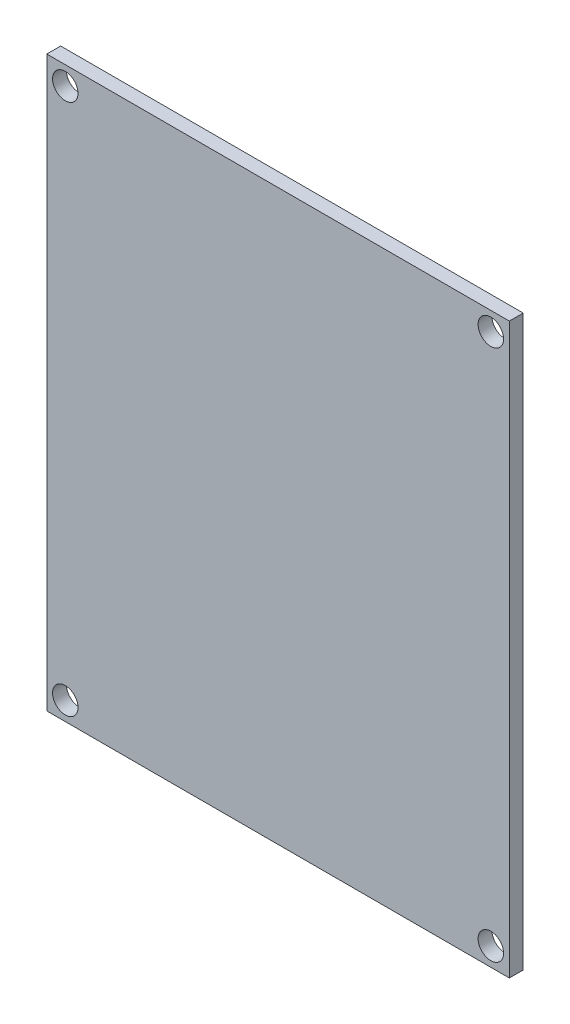
SolidWorks part; units mm, degrees
ref_plane "Front Plane" through (0, 0, 0) normal (0, 0, 1) x (1, 0, 0)
ref_plane "Top Plane" through (0, 0, 0) normal (0, 1, 0) x (1, 0, 0)
ref_plane "Right Plane" through (0, 0, 0) normal (1, 0, 0) x (0, 0, -1)
sketch "Model" plane through (0, 0, 0) normal (0, 0, 1) x (1, 0, 0)
  line L0 (84.1673, 32.1811) -> (4.1672, 32.1811)
  line L1 (84.1673, 130.5807) -> (84.1673, 32.1811)
  line L2 (4.1672, 130.5807) -> (84.1673, 130.5807)
  line L3 (4.1672, 32.1811) -> (4.1672, 130.5807)
  line L4 (36.7661, 123.577) -> (38.7714, 123.577)
  line L5 (38.7714, 123.577) -> (38.7714, 125.5823)
  line L6 (38.7714, 125.5823) -> (36.7661, 125.5823)
  line L7 (36.7661, 125.5823) -> (36.7661, 123.577)
  line L8 (62.7636, 124.3784) -> (64.7689, 124.3784)
  line L9 (64.7689, 124.3784) -> (64.7689, 126.3837)
  line L10 (64.7689, 126.3837) -> (62.7636, 126.3837)
  line L11 (62.7636, 126.3837) -> (62.7636, 124.3784)
  line L12 (5.8947, 120.0139) -> (7.5208, 120.0139)
  line L13 (7.5208, 120.0139) -> (7.5208, 121.64)
  line L14 (7.5208, 121.64) -> (5.8947, 121.64)
  line L15 (5.8947, 121.64) -> (5.8947, 120.0139)
  line L16 (5.8947, 103.7586) -> (7.5208, 103.7586)
  line L17 (7.5208, 103.7586) -> (7.5208, 105.3846)
  line L18 (7.5208, 105.3846) -> (5.8947, 105.3846)
  line L19 (5.8947, 105.3846) -> (5.8947, 103.7586)
  line L20 (5.8947, 87.5021) -> (7.5208, 87.5021)
  line L21 (7.5208, 87.5021) -> (7.5208, 89.1282)
  line L22 (7.5208, 89.1282) -> (5.8947, 89.1282)
  line L23 (5.8947, 89.1282) -> (5.8947, 87.5021)
  line L24 (5.8947, 71.2457) -> (7.5208, 71.2457)
  line L25 (7.5208, 71.2457) -> (7.5208, 72.8718)
  line L26 (7.5208, 72.8718) -> (5.8947, 72.8718)
  line L27 (5.8947, 72.8718) -> (5.8947, 71.2457)
  line L28 (5.8947, 54.9903) -> (7.5208, 54.9903)
  line L29 (7.5208, 54.9903) -> (7.5208, 56.6164)
  line L30 (7.5208, 56.6164) -> (5.8947, 56.6164)
  line L31 (5.8947, 56.6164) -> (5.8947, 54.9903)
  line L32 (69.5711, 125.1678) -> (71.1972, 125.1678)
  line L33 (71.1972, 125.1678) -> (71.1972, 126.7938)
  line L34 (71.1972, 126.7938) -> (69.5711, 126.7938)
  line L35 (69.5711, 126.7938) -> (69.5711, 125.1678)
  line L36 (5.8947, 46.8621) -> (7.5208, 46.8621)
  line L37 (7.5208, 46.8621) -> (7.5208, 48.4882)
  line L38 (7.5208, 48.4882) -> (5.8947, 48.4882)
  line L39 (5.8947, 48.4882) -> (5.8947, 46.8621)
  line L40 (5.8947, 40.7657) -> (7.5208, 40.7657)
  line L41 (7.5208, 40.7657) -> (7.5208, 42.3918)
  line L42 (7.5208, 42.3918) -> (5.8947, 42.3918)
  line L43 (5.8947, 42.3918) -> (5.8947, 40.7657)
  line L44 (43.1315, 46.4697) -> (44.3387, 46.4697)
  line L45 (44.3387, 46.4697) -> (44.3387, 47.6768)
  line L46 (44.3387, 47.6768) -> (43.1315, 47.6768)
  line L47 (43.1315, 47.6768) -> (43.1315, 46.4697)
  line L48 (47.571, 110.5672) -> (49.1971, 110.5672)
  line L49 (49.1971, 110.5672) -> (49.1971, 112.1933)
  line L50 (49.1971, 112.1933) -> (47.571, 112.1933)
  line L51 (47.571, 112.1933) -> (47.571, 110.5672)
  line L52 (79.138, 119.3513) -> (80.7641, 119.3513)
  line L53 (80.7641, 119.3513) -> (80.7641, 120.9774)
  line L54 (80.7641, 120.9774) -> (79.138, 120.9774)
  line L55 (79.138, 120.9774) -> (79.138, 119.3513)
  line L56 (39.5839, 36.2799) -> (39.5839, 36.0803)
  line L57 (40.7899, 36.0803) -> (40.7899, 36.2799)
  line L58 (43.1436, 36.2799) -> (43.1436, 36.0803)
  line L59 (44.3508, 36.0803) -> (44.3508, 36.2799)
  line L60 (44.2835, 33.7156) -> (44.2835, 33.5558)
  line L61 (46.2095, 33.5558) -> (46.2095, 33.7156)
  line L62 (37.7241, 33.7156) -> (37.7241, 33.5558)
  line L63 (39.65, 33.5558) -> (39.65, 33.7156)
  line L64 (67.202, 45.6494) -> (68.828, 45.6494)
  line L65 (68.828, 45.6494) -> (68.828, 47.2755)
  line L66 (68.828, 47.2755) -> (67.202, 47.2755)
  line L67 (67.202, 47.2755) -> (67.202, 45.6494)
  line L68 (24.7396, 63.1693) -> (26.3657, 63.1693)
  line L69 (26.3657, 63.1693) -> (26.3657, 64.7954)
  line L70 (26.3657, 64.7954) -> (24.7396, 64.7954)
  line L71 (24.7396, 64.7954) -> (24.7396, 63.1693)
  line L72 (24.7396, 60.9688) -> (26.3657, 60.9688)
  line L73 (26.3657, 60.9688) -> (26.3657, 62.5949)
  line L74 (26.3657, 62.5949) -> (24.7396, 62.5949)
  line L75 (24.7396, 62.5949) -> (24.7396, 60.9688)
  line L76 (24.7396, 93.3682) -> (26.3657, 93.3682)
  line L77 (26.3657, 93.3682) -> (26.3657, 94.9942)
  line L78 (26.3657, 94.9942) -> (24.7396, 94.9942)
  line L79 (24.7396, 94.9942) -> (24.7396, 93.3682)
  line L80 (24.7396, 95.5675) -> (26.3657, 95.5675)
  line L81 (26.3657, 95.5675) -> (26.3657, 97.1936)
  line L82 (26.3657, 97.1936) -> (24.7396, 97.1936)
  line L83 (24.7396, 97.1936) -> (24.7396, 95.5675)
  line L84 (24.7396, 79.3684) -> (26.3657, 79.3684)
  line L85 (26.3657, 79.3684) -> (26.3657, 80.9945)
  line L86 (26.3657, 80.9945) -> (24.7396, 80.9945)
  line L87 (24.7396, 80.9945) -> (24.7396, 79.3684)
  line L88 (24.7396, 77.1679) -> (26.3657, 77.1679)
  line L89 (26.3657, 77.1679) -> (26.3657, 78.794)
  line L90 (26.3657, 78.794) -> (24.7396, 78.794)
  line L91 (24.7396, 78.794) -> (24.7396, 77.1679)
  line L92 (24.7396, 109.3688) -> (26.3657, 109.3688)
  line L93 (26.3657, 109.3688) -> (26.3657, 110.9949)
  line L94 (26.3657, 110.9949) -> (24.7396, 110.9949)
  line L95 (24.7396, 110.9949) -> (24.7396, 109.3688)
  line L96 (24.7396, 111.5693) -> (26.3657, 111.5693)
  line L97 (26.3657, 111.5693) -> (26.3657, 113.1954)
  line L98 (26.3657, 113.1954) -> (24.7396, 113.1954)
  line L99 (24.7396, 113.1954) -> (24.7396, 111.5693)
  line L100 (39.3623, 114.5525) -> (40.9884, 114.5525)
  line L101 (40.9884, 114.5525) -> (40.9884, 116.1785)
  line L102 (40.9884, 116.1785) -> (39.3623, 116.1785)
  line L103 (39.3623, 116.1785) -> (39.3623, 114.5525)
  line L104 (9.9594, 103.7586) -> (11.5854, 103.7586)
  line L105 (11.5854, 103.7586) -> (11.5854, 105.3846)
  line L106 (11.5854, 105.3846) -> (9.9594, 105.3846)
  line L107 (9.9594, 105.3846) -> (9.9594, 103.7586)
  line L108 (84.1673, 32.1811) -> (4.1672, 32.1811)
  line L109 (84.1673, 130.5807) -> (84.1673, 32.1811)
  line L110 (4.1672, 130.5807) -> (84.1673, 130.5807)
  line L111 (4.1672, 32.1811) -> (4.1672, 130.5807)
  spline S0 degree 3 poles (44.9703, 124.5802) (44.9703, 126.1842) (42.5648, 126.1842) (42.5648, 124.5802) knots 0 0 0 0 1 1 1 1
  spline S1 degree 3 poles (42.5648, 124.5802) (42.5648, 122.9761) (44.9703, 122.9761) (44.9703, 124.5802) knots 0 0 0 0 1 1 1 1
  spline S2 degree 3 poles (60.9699, 125.3805) (60.9699, 126.9846) (58.5644, 126.9846) (58.5644, 125.3805) knots 0 0 0 0 1 1 1 1
  spline S3 degree 3 poles (58.5644, 125.3805) (58.5644, 123.7765) (60.9699, 123.7765) (60.9699, 125.3805) knots 0 0 0 0 1 1 1 1
  spline S4 degree 3 poles (7.5208, 118.7946) (7.5208, 119.8783) (5.8947, 119.8783) (5.8947, 118.7946) knots 0 0 0 0 1 1 1 1
  spline S5 degree 3 poles (5.8947, 118.7946) (5.8947, 117.7109) (7.5208, 117.7109) (7.5208, 118.7946) knots 0 0 0 0 1 1 1 1
  spline S6 degree 3 poles (7.5208, 116.7628) (7.5208, 117.8465) (5.8947, 117.8465) (5.8947, 116.7628) knots 0 0 0 0 1 1 1 1
  spline S7 degree 3 poles (5.8947, 116.7628) (5.8947, 115.6791) (7.5208, 115.6791) (7.5208, 116.7628) knots 0 0 0 0 1 1 1 1
  spline S8 degree 3 poles (7.5208, 114.731) (7.5208, 115.8147) (5.8947, 115.8147) (5.8947, 114.731) knots 0 0 0 0 1 1 1 1
  spline S9 degree 3 poles (5.8947, 114.731) (5.8947, 113.6474) (7.5208, 113.6474) (7.5208, 114.731) knots 0 0 0 0 1 1 1 1
  spline S10 degree 3 poles (7.5208, 112.6993) (7.5208, 113.783) (5.8947, 113.783) (5.8947, 112.6993) knots 0 0 0 0 1 1 1 1
  spline S11 degree 3 poles (5.8947, 112.6993) (5.8947, 111.6156) (7.5208, 111.6156) (7.5208, 112.6993) knots 0 0 0 0 1 1 1 1
  spline S12 degree 3 poles (7.5208, 110.6675) (7.5208, 111.7512) (5.8947, 111.7512) (5.8947, 110.6675) knots 0 0 0 0 1 1 1 1
  spline S13 degree 3 poles (5.8947, 110.6675) (5.8947, 109.5827) (7.5208, 109.5827) (7.5208, 110.6675) knots 0 0 0 0 1 1 1 1
  spline S14 degree 3 poles (7.5208, 108.6346) (7.5208, 109.7183) (5.8947, 109.7183) (5.8947, 108.6346) knots 0 0 0 0 1 1 1 1
  spline S15 degree 3 poles (5.8947, 108.6346) (5.8947, 107.5509) (7.5208, 107.5509) (7.5208, 108.6346) knots 0 0 0 0 1 1 1 1
  spline S16 degree 3 poles (7.5208, 102.5393) (7.5208, 103.623) (5.8947, 103.623) (5.8947, 102.5393) knots 0 0 0 0 1 1 1 1
  spline S17 degree 3 poles (5.8947, 102.5393) (5.8947, 101.4556) (7.5208, 101.4556) (7.5208, 102.5393) knots 0 0 0 0 1 1 1 1
  spline S18 degree 3 poles (7.5208, 100.5075) (7.5208, 101.5912) (5.8947, 101.5912) (5.8947, 100.5075) knots 0 0 0 0 1 1 1 1
  spline S19 degree 3 poles (5.8947, 100.5075) (5.8947, 99.4227) (7.5208, 99.4227) (7.5208, 100.5075) knots 0 0 0 0 1 1 1 1
  spline S20 degree 3 poles (7.5208, 98.4746) (7.5208, 99.5583) (5.8947, 99.5583) (5.8947, 98.4746) knots 0 0 0 0 1 1 1 1
  spline S21 degree 3 poles (5.8947, 98.4746) (5.8947, 97.3909) (7.5208, 97.3909) (7.5208, 98.4746) knots 0 0 0 0 1 1 1 1
  spline S22 degree 3 poles (7.5208, 96.4428) (7.5208, 97.5265) (5.8947, 97.5265) (5.8947, 96.4428) knots 0 0 0 0 1 1 1 1
  spline S23 degree 3 poles (5.8947, 96.4428) (5.8947, 95.3591) (7.5208, 95.3591) (7.5208, 96.4428) knots 0 0 0 0 1 1 1 1
  spline S24 degree 3 poles (7.5208, 94.4111) (7.5208, 95.4947) (5.8947, 95.4947) (5.8947, 94.4111) knots 0 0 0 0 1 1 1 1
  spline S25 degree 3 poles (5.8947, 94.4111) (5.8947, 93.3274) (7.5208, 93.3274) (7.5208, 94.4111) knots 0 0 0 0 1 1 1 1
  spline S26 degree 3 poles (7.5208, 92.3793) (7.5208, 93.463) (5.8947, 93.463) (5.8947, 92.3793) knots 0 0 0 0 1 1 1 1
  spline S27 degree 3 poles (5.8947, 92.3793) (5.8947, 91.2956) (7.5208, 91.2956) (7.5208, 92.3793) knots 0 0 0 0 1 1 1 1
  spline S28 degree 3 poles (7.5208, 86.2828) (7.5208, 87.3665) (5.8947, 87.3665) (5.8947, 86.2828) knots 0 0 0 0 1 1 1 1
  spline S29 degree 3 poles (5.8947, 86.2828) (5.8947, 85.1991) (7.5208, 85.1991) (7.5208, 86.2828) knots 0 0 0 0 1 1 1 1
  spline S30 degree 3 poles (7.5208, 84.2511) (7.5208, 85.3347) (5.8947, 85.3347) (5.8947, 84.2511) knots 0 0 0 0 1 1 1 1
  spline S31 degree 3 poles (5.8947, 84.2511) (5.8947, 83.1674) (7.5208, 83.1674) (7.5208, 84.2511) knots 0 0 0 0 1 1 1 1
  spline S32 degree 3 poles (7.5208, 82.2193) (7.5208, 83.303) (5.8947, 83.303) (5.8947, 82.2193) knots 0 0 0 0 1 1 1 1
  spline S33 degree 3 poles (5.8947, 82.2193) (5.8947, 81.1356) (7.5208, 81.1356) (7.5208, 82.2193) knots 0 0 0 0 1 1 1 1
  spline S34 degree 3 poles (7.5208, 80.1875) (7.5208, 81.2712) (5.8947, 81.2712) (5.8947, 80.1875) knots 0 0 0 0 1 1 1 1
  spline S35 degree 3 poles (5.8947, 80.1875) (5.8947, 79.1027) (7.5208, 79.1027) (7.5208, 80.1875) knots 0 0 0 0 1 1 1 1
  spline S36 degree 3 poles (7.5208, 78.1546) (7.5208, 79.2383) (5.8947, 79.2383) (5.8947, 78.1546) knots 0 0 0 0 1 1 1 1
  spline S37 degree 3 poles (5.8947, 78.1546) (5.8947, 77.0709) (7.5208, 77.0709) (7.5208, 78.1546) knots 0 0 0 0 1 1 1 1
  spline S38 degree 3 poles (7.5208, 76.1228) (7.5208, 77.2065) (5.8947, 77.2065) (5.8947, 76.1228) knots 0 0 0 0 1 1 1 1
  spline S39 degree 3 poles (5.8947, 76.1228) (5.8947, 75.0391) (7.5208, 75.0391) (7.5208, 76.1228) knots 0 0 0 0 1 1 1 1
  spline S40 degree 3 poles (7.5208, 70.0275) (7.5208, 71.1112) (5.8947, 71.1112) (5.8947, 70.0275) knots 0 0 0 0 1 1 1 1
  spline S41 degree 3 poles (5.8947, 70.0275) (5.8947, 68.9427) (7.5208, 68.9427) (7.5208, 70.0275) knots 0 0 0 0 1 1 1 1
  spline S42 degree 3 poles (7.5208, 67.9946) (7.5208, 69.0783) (5.8947, 69.0783) (5.8947, 67.9946) knots 0 0 0 0 1 1 1 1
  spline S43 degree 3 poles (5.8947, 67.9946) (5.8947, 66.9109) (7.5208, 66.9109) (7.5208, 67.9946) knots 0 0 0 0 1 1 1 1
  spline S44 degree 3 poles (7.5208, 65.9628) (7.5208, 67.0465) (5.8947, 67.0465) (5.8947, 65.9628) knots 0 0 0 0 1 1 1 1
  spline S45 degree 3 poles (5.8947, 65.9628) (5.8947, 64.8791) (7.5208, 64.8791) (7.5208, 65.9628) knots 0 0 0 0 1 1 1 1
  spline S46 degree 3 poles (7.5208, 63.9311) (7.5208, 65.0147) (5.8947, 65.0147) (5.8947, 63.9311) knots 0 0 0 0 1 1 1 1
  spline S47 degree 3 poles (5.8947, 63.9311) (5.8947, 62.8474) (7.5208, 62.8474) (7.5208, 63.9311) knots 0 0 0 0 1 1 1 1
  spline S48 degree 3 poles (7.5208, 61.8993) (7.5208, 62.983) (5.8947, 62.983) (5.8947, 61.8993) knots 0 0 0 0 1 1 1 1
  spline S49 degree 3 poles (5.8947, 61.8993) (5.8947, 60.8156) (7.5208, 60.8156) (7.5208, 61.8993) knots 0 0 0 0 1 1 1 1
  spline S50 degree 3 poles (7.5208, 59.8675) (7.5208, 60.9512) (5.8947, 60.9512) (5.8947, 59.8675) knots 0 0 0 0 1 1 1 1
  spline S51 degree 3 poles (5.8947, 59.8675) (5.8947, 58.7827) (7.5208, 58.7827) (7.5208, 59.8675) knots 0 0 0 0 1 1 1 1
  spline S52 degree 3 poles (7.5208, 53.7711) (7.5208, 54.8547) (5.8947, 54.8547) (5.8947, 53.7711) knots 0 0 0 0 1 1 1 1
  spline S53 degree 3 poles (5.8947, 53.7711) (5.8947, 52.6874) (7.5208, 52.6874) (7.5208, 53.7711) knots 0 0 0 0 1 1 1 1
  spline S54 degree 3 poles (7.5208, 51.7393) (7.5208, 52.823) (5.8947, 52.823) (5.8947, 51.7393) knots 0 0 0 0 1 1 1 1
  spline S55 degree 3 poles (5.8947, 51.7393) (5.8947, 50.6556) (7.5208, 50.6556) (7.5208, 51.7393) knots 0 0 0 0 1 1 1 1
  spline S56 degree 3 poles (7.5208, 49.7075) (7.5208, 50.7912) (5.8947, 50.7912) (5.8947, 49.7075) knots 0 0 0 0 1 1 1 1
  spline S57 degree 3 poles (5.8947, 49.7075) (5.8947, 48.6227) (7.5208, 48.6227) (7.5208, 49.7075) knots 0 0 0 0 1 1 1 1
  spline S58 degree 3 poles (69.1654, 125.9803) (69.1654, 127.0639) (67.5393, 127.0639) (67.5393, 125.9803) knots 0 0 0 0 1 1 1 1
  spline S59 degree 3 poles (67.5393, 125.9803) (67.5393, 124.8966) (69.1654, 124.8966) (69.1654, 125.9803) knots 0 0 0 0 1 1 1 1
  spline S60 degree 3 poles (7.5208, 45.6428) (7.5208, 46.7265) (5.8947, 46.7265) (5.8947, 45.6428) knots 0 0 0 0 1 1 1 1
  spline S61 degree 3 poles (5.8947, 45.6428) (5.8947, 44.5591) (7.5208, 44.5591) (7.5208, 45.6428) knots 0 0 0 0 1 1 1 1
  spline S62 degree 3 poles (7.5208, 39.5475) (7.5208, 40.6312) (5.8947, 40.6312) (5.8947, 39.5475) knots 0 0 0 0 1 1 1 1
  spline S63 degree 3 poles (5.8947, 39.5475) (5.8947, 38.4627) (7.5208, 38.4627) (7.5208, 39.5475) knots 0 0 0 0 1 1 1 1
  spline S64 degree 3 poles (44.3387, 48.0891) (44.3387, 48.8939) (43.1315, 48.8939) (43.1315, 48.0891) knots 0 0 0 0 1 1 1 1
  spline S65 degree 3 poles (43.1315, 48.0891) (43.1315, 47.2843) (44.3387, 47.2843) (44.3387, 48.0891) knots 0 0 0 0 1 1 1 1
  spline S66 degree 3 poles (45.354, 47.0738) (45.354, 47.8786) (44.1468, 47.8786) (44.1468, 47.0738) knots 0 0 0 0 1 1 1 1
  spline S67 degree 3 poles (44.1468, 47.0738) (44.1468, 46.269) (45.354, 46.269) (45.354, 47.0738) knots 0 0 0 0 1 1 1 1
  spline S68 degree 3 poles (45.354, 48.0891) (45.354, 48.8939) (44.1468, 48.8939) (44.1468, 48.0891) knots 0 0 0 0 1 1 1 1
  spline S69 degree 3 poles (44.1468, 48.0891) (44.1468, 47.2843) (45.354, 47.2843) (45.354, 48.0891) knots 0 0 0 0 1 1 1 1
  spline S70 degree 3 poles (46.3704, 47.0738) (46.3704, 47.8786) (45.1633, 47.8786) (45.1633, 47.0738) knots 0 0 0 0 1 1 1 1
  spline S71 degree 3 poles (45.1633, 47.0738) (45.1633, 46.269) (46.3704, 46.269) (46.3704, 47.0738) knots 0 0 0 0 1 1 1 1
  spline S72 degree 3 poles (46.3704, 48.0891) (46.3704, 48.8939) (45.1633, 48.8939) (45.1633, 48.0891) knots 0 0 0 0 1 1 1 1
  spline S73 degree 3 poles (45.1633, 48.0891) (45.1633, 47.2843) (46.3704, 47.2843) (46.3704, 48.0891) knots 0 0 0 0 1 1 1 1
  spline S74 degree 3 poles (47.3858, 47.0738) (47.3858, 47.8786) (46.1797, 47.8786) (46.1797, 47.0738) knots 0 0 0 0 1 1 1 1
  spline S75 degree 3 poles (46.1797, 47.0738) (46.1797, 46.269) (47.3858, 46.269) (47.3858, 47.0738) knots 0 0 0 0 1 1 1 1
  spline S76 degree 3 poles (47.3858, 48.0891) (47.3858, 48.8939) (46.1797, 48.8939) (46.1797, 48.0891) knots 0 0 0 0 1 1 1 1
  spline S77 degree 3 poles (46.1797, 48.0891) (46.1797, 47.2843) (47.3858, 47.2843) (47.3858, 48.0891) knots 0 0 0 0 1 1 1 1
  spline S78 degree 3 poles (48.4022, 47.0738) (48.4022, 47.8786) (47.1951, 47.8786) (47.1951, 47.0738) knots 0 0 0 0 1 1 1 1
  spline S79 degree 3 poles (47.1951, 47.0738) (47.1951, 46.269) (48.4022, 46.269) (48.4022, 47.0738) knots 0 0 0 0 1 1 1 1
  spline S80 degree 3 poles (48.4022, 48.0891) (48.4022, 48.8939) (47.1951, 48.8939) (47.1951, 48.0891) knots 0 0 0 0 1 1 1 1
  spline S81 degree 3 poles (47.1951, 48.0891) (47.1951, 47.2843) (48.4022, 47.2843) (48.4022, 48.0891) knots 0 0 0 0 1 1 1 1
  spline S82 degree 3 poles (47.1653, 111.3797) (47.1653, 112.4645) (45.5392, 112.4645) (45.5392, 111.3797) knots 0 0 0 0 1 1 1 1
  spline S83 degree 3 poles (45.5392, 111.3797) (45.5392, 110.296) (47.1653, 110.296) (47.1653, 111.3797) knots 0 0 0 0 1 1 1 1
  spline S84 degree 3 poles (51.4284, 35.9811) (51.4284, 36.7859) (50.2212, 36.7859) (50.2212, 35.9811) knots 0 0 0 0 1 1 1 1
  spline S85 degree 3 poles (50.2212, 35.9811) (50.2212, 35.1764) (51.4284, 35.1764) (51.4284, 35.9811) knots 0 0 0 0 1 1 1 1
  spline S86 degree 3 poles (57.8126, 35.9811) (57.8126, 36.7859) (56.6054, 36.7859) (56.6054, 35.9811) knots 0 0 0 0 1 1 1 1
  spline S87 degree 3 poles (56.6054, 35.9811) (56.6054, 35.1764) (57.8126, 35.1764) (57.8126, 35.9811) knots 0 0 0 0 1 1 1 1
  spline S88 degree 3 poles (82.7958, 120.1649) (82.7958, 121.2486) (81.1698, 121.2486) (81.1698, 120.1649) knots 0 0 0 0 1 1 1 1
  spline S89 degree 3 poles (81.1698, 120.1649) (81.1698, 119.0812) (82.7958, 119.0812) (82.7958, 120.1649) knots 0 0 0 0 1 1 1 1
  spline S90 degree 3 poles (80.7641, 110.0049) (80.7641, 111.0886) (79.138, 111.0886) (79.138, 110.0049) knots 0 0 0 0 1 1 1 1
  spline S91 degree 3 poles (79.138, 110.0049) (79.138, 108.9212) (80.7641, 108.9212) (80.7641, 110.0049) knots 0 0 0 0 1 1 1 1
  spline S92 degree 3 poles (82.7958, 118.132) (82.7958, 119.2157) (81.1698, 119.2157) (81.1698, 118.132) knots 0 0 0 0 1 1 1 1
  spline S93 degree 3 poles (81.1698, 118.132) (81.1698, 117.0484) (82.7958, 117.0484) (82.7958, 118.132) knots 0 0 0 0 1 1 1 1
  spline S94 degree 3 poles (80.7641, 107.972) (80.7641, 109.0557) (79.138, 109.0557) (79.138, 107.972) knots 0 0 0 0 1 1 1 1
  spline S95 degree 3 poles (79.138, 107.972) (79.138, 106.8884) (80.7641, 106.8884) (80.7641, 107.972) knots 0 0 0 0 1 1 1 1
  spline S96 degree 3 poles (82.7958, 116.1003) (82.7958, 117.184) (81.1698, 117.184) (81.1698, 116.1003) knots 0 0 0 0 1 1 1 1
  spline S97 degree 3 poles (81.1698, 116.1003) (81.1698, 115.0166) (82.7958, 115.0166) (82.7958, 116.1003) knots 0 0 0 0 1 1 1 1
  spline S98 degree 3 poles (80.7641, 105.9403) (80.7641, 107.024) (79.138, 107.024) (79.138, 105.9403) knots 0 0 0 0 1 1 1 1
  spline S99 degree 3 poles (79.138, 105.9403) (79.138, 104.8566) (80.7641, 104.8566) (80.7641, 105.9403) knots 0 0 0 0 1 1 1 1
  spline S100 degree 3 poles (82.7958, 114.0685) (82.7958, 115.1522) (81.1698, 115.1522) (81.1698, 114.0685) knots 0 0 0 0 1 1 1 1
  spline S101 degree 3 poles (81.1698, 114.0685) (81.1698, 112.9848) (82.7958, 112.9848) (82.7958, 114.0685) knots 0 0 0 0 1 1 1 1
  spline S102 degree 3 poles (80.7641, 103.9085) (80.7641, 104.9922) (79.138, 104.9922) (79.138, 103.9085) knots 0 0 0 0 1 1 1 1
  spline S103 degree 3 poles (79.138, 103.9085) (79.138, 102.8248) (80.7641, 102.8248) (80.7641, 103.9085) knots 0 0 0 0 1 1 1 1
  spline S104 degree 3 poles (82.7958, 112.0367) (82.7958, 113.1204) (81.1698, 113.1204) (81.1698, 112.0367) knots 0 0 0 0 1 1 1 1
  spline S105 degree 3 poles (81.1698, 112.0367) (81.1698, 110.953) (82.7958, 110.953) (82.7958, 112.0367) knots 0 0 0 0 1 1 1 1
  spline S106 degree 3 poles (80.7641, 101.8767) (80.7641, 102.9604) (79.138, 102.9604) (79.138, 101.8767) knots 0 0 0 0 1 1 1 1
  spline S107 degree 3 poles (79.138, 101.8767) (79.138, 100.793) (80.7641, 100.793) (80.7641, 101.8767) knots 0 0 0 0 1 1 1 1
  spline S108 degree 3 poles (82.7958, 110.0049) (82.7958, 111.0886) (81.1698, 111.0886) (81.1698, 110.0049) knots 0 0 0 0 1 1 1 1
  spline S109 degree 3 poles (81.1698, 110.0049) (81.1698, 108.9212) (82.7958, 108.9212) (82.7958, 110.0049) knots 0 0 0 0 1 1 1 1
  spline S110 degree 3 poles (80.7641, 99.8449) (80.7641, 100.9286) (79.138, 100.9286) (79.138, 99.8449) knots 0 0 0 0 1 1 1 1
  spline S111 degree 3 poles (79.138, 99.8449) (79.138, 98.7612) (80.7641, 98.7612) (80.7641, 99.8449) knots 0 0 0 0 1 1 1 1
  spline S112 degree 3 poles (82.7958, 107.972) (82.7958, 109.0557) (81.1698, 109.0557) (81.1698, 107.972) knots 0 0 0 0 1 1 1 1
  spline S113 degree 3 poles (81.1698, 107.972) (81.1698, 106.8884) (82.7958, 106.8884) (82.7958, 107.972) knots 0 0 0 0 1 1 1 1
  spline S114 degree 3 poles (80.7641, 97.812) (80.7641, 98.8957) (79.138, 98.8957) (79.138, 97.812) knots 0 0 0 0 1 1 1 1
  spline S115 degree 3 poles (79.138, 97.812) (79.138, 96.7284) (80.7641, 96.7284) (80.7641, 97.812) knots 0 0 0 0 1 1 1 1
  spline S116 degree 3 poles (82.7958, 105.9403) (82.7958, 107.024) (81.1698, 107.024) (81.1698, 105.9403) knots 0 0 0 0 1 1 1 1
  spline S117 degree 3 poles (81.1698, 105.9403) (81.1698, 104.8566) (82.7958, 104.8566) (82.7958, 105.9403) knots 0 0 0 0 1 1 1 1
  spline S118 degree 3 poles (80.7641, 95.7803) (80.7641, 96.864) (79.138, 96.864) (79.138, 95.7803) knots 0 0 0 0 1 1 1 1
  spline S119 degree 3 poles (79.138, 95.7803) (79.138, 94.6966) (80.7641, 94.6966) (80.7641, 95.7803) knots 0 0 0 0 1 1 1 1
  spline S120 degree 3 poles (82.7958, 103.9085) (82.7958, 104.9922) (81.1698, 104.9922) (81.1698, 103.9085) knots 0 0 0 0 1 1 1 1
  spline S121 degree 3 poles (81.1698, 103.9085) (81.1698, 102.8248) (82.7958, 102.8248) (82.7958, 103.9085) knots 0 0 0 0 1 1 1 1
  spline S122 degree 3 poles (80.7641, 93.7485) (80.7641, 94.8322) (79.138, 94.8322) (79.138, 93.7485) knots 0 0 0 0 1 1 1 1
  spline S123 degree 3 poles (79.138, 93.7485) (79.138, 92.6648) (80.7641, 92.6648) (80.7641, 93.7485) knots 0 0 0 0 1 1 1 1
  spline S124 degree 3 poles (82.7958, 101.8767) (82.7958, 102.9604) (81.1698, 102.9604) (81.1698, 101.8767) knots 0 0 0 0 1 1 1 1
  spline S125 degree 3 poles (81.1698, 101.8767) (81.1698, 100.793) (82.7958, 100.793) (82.7958, 101.8767) knots 0 0 0 0 1 1 1 1
  spline S126 degree 3 poles (80.7641, 91.7167) (80.7641, 92.8004) (79.138, 92.8004) (79.138, 91.7167) knots 0 0 0 0 1 1 1 1
  spline S127 degree 3 poles (79.138, 91.7167) (79.138, 90.633) (80.7641, 90.633) (80.7641, 91.7167) knots 0 0 0 0 1 1 1 1
  spline S128 degree 3 poles (82.7958, 99.8449) (82.7958, 100.9286) (81.1698, 100.9286) (81.1698, 99.8449) knots 0 0 0 0 1 1 1 1
  spline S129 degree 3 poles (81.1698, 99.8449) (81.1698, 98.7612) (82.7958, 98.7612) (82.7958, 99.8449) knots 0 0 0 0 1 1 1 1
  spline S130 degree 3 poles (80.7641, 89.6849) (80.7641, 90.7686) (79.138, 90.7686) (79.138, 89.6849) knots 0 0 0 0 1 1 1 1
  spline S131 degree 3 poles (79.138, 89.6849) (79.138, 88.6012) (80.7641, 88.6012) (80.7641, 89.6849) knots 0 0 0 0 1 1 1 1
  spline S132 degree 3 poles (82.7958, 97.812) (82.7958, 98.8957) (81.1698, 98.8957) (81.1698, 97.812) knots 0 0 0 0 1 1 1 1
  spline S133 degree 3 poles (81.1698, 97.812) (81.1698, 96.7284) (82.7958, 96.7284) (82.7958, 97.812) knots 0 0 0 0 1 1 1 1
  spline S134 degree 3 poles (82.7958, 95.7803) (82.7958, 96.864) (81.1698, 96.864) (81.1698, 95.7803) knots 0 0 0 0 1 1 1 1
  spline S135 degree 3 poles (81.1698, 95.7803) (81.1698, 94.6966) (82.7958, 94.6966) (82.7958, 95.7803) knots 0 0 0 0 1 1 1 1
  spline S136 degree 3 poles (80.7641, 87.652) (80.7641, 88.7357) (79.138, 88.7357) (79.138, 87.652) knots 0 0 0 0 1 1 1 1
  spline S137 degree 3 poles (79.138, 87.652) (79.138, 86.5684) (80.7641, 86.5684) (80.7641, 87.652) knots 0 0 0 0 1 1 1 1
  spline S138 degree 3 poles (82.7958, 93.7485) (82.7958, 94.8322) (81.1698, 94.8322) (81.1698, 93.7485) knots 0 0 0 0 1 1 1 1
  spline S139 degree 3 poles (81.1698, 93.7485) (81.1698, 92.6648) (82.7958, 92.6648) (82.7958, 93.7485) knots 0 0 0 0 1 1 1 1
  spline S140 degree 3 poles (82.7958, 89.6849) (82.7958, 90.7686) (81.1698, 90.7686) (81.1698, 89.6849) knots 0 0 0 0 1 1 1 1
  spline S141 degree 3 poles (81.1698, 89.6849) (81.1698, 88.6012) (82.7958, 88.6012) (82.7958, 89.6849) knots 0 0 0 0 1 1 1 1
  spline S142 degree 3 poles (82.7958, 87.652) (82.7958, 88.7357) (81.1698, 88.7357) (81.1698, 87.652) knots 0 0 0 0 1 1 1 1
  spline S143 degree 3 poles (81.1698, 87.652) (81.1698, 86.5684) (82.7958, 86.5684) (82.7958, 87.652) knots 0 0 0 0 1 1 1 1
  spline S144 degree 3 poles (82.7958, 85.6203) (82.7958, 86.704) (81.1698, 86.704) (81.1698, 85.6203) knots 0 0 0 0 1 1 1 1
  spline S145 degree 3 poles (81.1698, 85.6203) (81.1698, 84.5366) (82.7958, 84.5366) (82.7958, 85.6203) knots 0 0 0 0 1 1 1 1
  spline S146 degree 3 poles (82.7958, 83.5885) (82.7958, 84.6722) (81.1698, 84.6722) (81.1698, 83.5885) knots 0 0 0 0 1 1 1 1
  spline S147 degree 3 poles (81.1698, 83.5885) (81.1698, 82.5048) (82.7958, 82.5048) (82.7958, 83.5885) knots 0 0 0 0 1 1 1 1
  spline S148 degree 3 poles (80.7641, 85.6203) (80.7641, 86.704) (79.138, 86.704) (79.138, 85.6203) knots 0 0 0 0 1 1 1 1
  spline S149 degree 3 poles (79.138, 85.6203) (79.138, 84.5366) (80.7641, 84.5366) (80.7641, 85.6203) knots 0 0 0 0 1 1 1 1
  spline S150 degree 3 poles (80.7641, 83.5885) (80.7641, 84.6722) (79.138, 84.6722) (79.138, 83.5885) knots 0 0 0 0 1 1 1 1
  spline S151 degree 3 poles (79.138, 83.5885) (79.138, 82.5048) (80.7641, 82.5048) (80.7641, 83.5885) knots 0 0 0 0 1 1 1 1
  spline S152 degree 3 poles (80.7641, 118.132) (80.7641, 119.2157) (79.138, 119.2157) (79.138, 118.132) knots 0 0 0 0 1 1 1 1
  spline S153 degree 3 poles (79.138, 118.132) (79.138, 117.0484) (80.7641, 117.0484) (80.7641, 118.132) knots 0 0 0 0 1 1 1 1
  spline S154 degree 3 poles (80.7641, 116.1003) (80.7641, 117.184) (79.138, 117.184) (79.138, 116.1003) knots 0 0 0 0 1 1 1 1
  spline S155 degree 3 poles (79.138, 116.1003) (79.138, 115.0166) (80.7641, 115.0166) (80.7641, 116.1003) knots 0 0 0 0 1 1 1 1
  spline S156 degree 3 poles (80.7641, 114.0685) (80.7641, 115.1522) (79.138, 115.1522) (79.138, 114.0685) knots 0 0 0 0 1 1 1 1
  spline S157 degree 3 poles (79.138, 114.0685) (79.138, 112.9848) (80.7641, 112.9848) (80.7641, 114.0685) knots 0 0 0 0 1 1 1 1
  spline S158 degree 3 poles (80.7641, 112.0367) (80.7641, 113.1204) (79.138, 113.1204) (79.138, 112.0367) knots 0 0 0 0 1 1 1 1
  spline S159 degree 3 poles (79.138, 112.0367) (79.138, 110.953) (80.7641, 110.953) (80.7641, 112.0367) knots 0 0 0 0 1 1 1 1
  spline S160 degree 3 poles (80.7641, 81.5567) (80.7641, 82.6404) (79.138, 82.6404) (79.138, 81.5567) knots 0 0 0 0 1 1 1 1
  spline S161 degree 3 poles (79.138, 81.5567) (79.138, 80.473) (80.7641, 80.473) (80.7641, 81.5567) knots 0 0 0 0 1 1 1 1
  spline S162 degree 3 poles (82.7958, 81.5567) (82.7958, 82.6404) (81.1698, 82.6404) (81.1698, 81.5567) knots 0 0 0 0 1 1 1 1
  spline S163 degree 3 poles (81.1698, 81.5567) (81.1698, 80.473) (82.7958, 80.473) (82.7958, 81.5567) knots 0 0 0 0 1 1 1 1
  spline S164 degree 3 poles (82.7958, 91.7167) (82.7958, 92.8004) (81.1698, 92.8004) (81.1698, 91.7167) knots 0 0 0 0 1 1 1 1
  spline S165 degree 3 poles (81.1698, 91.7167) (81.1698, 90.633) (82.7958, 90.633) (82.7958, 91.7167) knots 0 0 0 0 1 1 1 1
  spline S166 degree 3 poles (80.7641, 79.5249) (80.7641, 80.6086) (79.138, 80.6086) (79.138, 79.5249) knots 0 0 0 0 1 1 1 1
  spline S167 degree 3 poles (79.138, 79.5249) (79.138, 78.4412) (80.7641, 78.4412) (80.7641, 79.5249) knots 0 0 0 0 1 1 1 1
  spline S168 degree 3 poles (82.7958, 79.5249) (82.7958, 80.6086) (81.1698, 80.6086) (81.1698, 79.5249) knots 0 0 0 0 1 1 1 1
  spline S169 degree 3 poles (81.1698, 79.5249) (81.1698, 78.4412) (82.7958, 78.4412) (82.7958, 79.5249) knots 0 0 0 0 1 1 1 1
  spline S170 degree 3 poles (80.7641, 77.492) (80.7641, 78.5757) (79.138, 78.5757) (79.138, 77.492) knots 0 0 0 0 1 1 1 1
  spline S171 degree 3 poles (79.138, 77.492) (79.138, 76.4084) (80.7641, 76.4084) (80.7641, 77.492) knots 0 0 0 0 1 1 1 1
  spline S172 degree 3 poles (82.7958, 77.492) (82.7958, 78.5757) (81.1698, 78.5757) (81.1698, 77.492) knots 0 0 0 0 1 1 1 1
  spline S173 degree 3 poles (81.1698, 77.492) (81.1698, 76.4084) (82.7958, 76.4084) (82.7958, 77.492) knots 0 0 0 0 1 1 1 1
  spline S174 degree 3 poles (80.7641, 75.4603) (80.7641, 76.544) (79.138, 76.544) (79.138, 75.4603) knots 0 0 0 0 1 1 1 1
  spline S175 degree 3 poles (79.138, 75.4603) (79.138, 74.3766) (80.7641, 74.3766) (80.7641, 75.4603) knots 0 0 0 0 1 1 1 1
  spline S176 degree 3 poles (82.7958, 75.4603) (82.7958, 76.544) (81.1698, 76.544) (81.1698, 75.4603) knots 0 0 0 0 1 1 1 1
  spline S177 degree 3 poles (81.1698, 75.4603) (81.1698, 74.3766) (82.7958, 74.3766) (82.7958, 75.4603) knots 0 0 0 0 1 1 1 1
  spline S178 degree 3 poles (80.7641, 73.4285) (80.7641, 74.5122) (79.138, 74.5122) (79.138, 73.4285) knots 0 0 0 0 1 1 1 1
  spline S179 degree 3 poles (79.138, 73.4285) (79.138, 72.3448) (80.7641, 72.3448) (80.7641, 73.4285) knots 0 0 0 0 1 1 1 1
  spline S180 degree 3 poles (82.7958, 73.4285) (82.7958, 74.5122) (81.1698, 74.5122) (81.1698, 73.4285) knots 0 0 0 0 1 1 1 1
  spline S181 degree 3 poles (81.1698, 73.4285) (81.1698, 72.3448) (82.7958, 72.3448) (82.7958, 73.4285) knots 0 0 0 0 1 1 1 1
  spline S182 degree 3 poles (80.7641, 71.3967) (80.7641, 72.4804) (79.138, 72.4804) (79.138, 71.3967) knots 0 0 0 0 1 1 1 1
  spline S183 degree 3 poles (79.138, 71.3967) (79.138, 70.313) (80.7641, 70.313) (80.7641, 71.3967) knots 0 0 0 0 1 1 1 1
  spline S184 degree 3 poles (82.7958, 71.3967) (82.7958, 72.4804) (81.1698, 72.4804) (81.1698, 71.3967) knots 0 0 0 0 1 1 1 1
  spline S185 degree 3 poles (81.1698, 71.3967) (81.1698, 70.313) (82.7958, 70.313) (82.7958, 71.3967) knots 0 0 0 0 1 1 1 1
  spline S186 degree 3 poles (40.7899, 36.2799) (40.7899, 37.0847) (39.5839, 37.0847) (39.5839, 36.2799) knots 0 0 0 0 1 1 1 1
  spline S187 degree 3 poles (39.5839, 36.0803) (39.5839, 35.2756) (40.7899, 35.2756) (40.7899, 36.0803) knots 0 0 0 0 1 1 1 1
  spline S188 degree 3 poles (44.3508, 36.2799) (44.3508, 37.0847) (43.1436, 37.0847) (43.1436, 36.2799) knots 0 0 0 0 1 1 1 1
  spline S189 degree 3 poles (43.1436, 36.0803) (43.1436, 35.2756) (44.3508, 35.2756) (44.3508, 36.0803) knots 0 0 0 0 1 1 1 1
  spline S190 degree 3 poles (46.2095, 33.7156) (46.2095, 35) (44.2835, 35) (44.2835, 33.7156) knots 0 0 0 0 1 1 1 1
  spline S191 degree 3 poles (44.2835, 33.5558) (44.2835, 32.2715) (46.2095, 32.2715) (46.2095, 33.5558) knots 0 0 0 0 1 1 1 1
  spline S192 degree 3 poles (39.65, 33.7156) (39.65, 35) (37.7241, 35) (37.7241, 33.7156) knots 0 0 0 0 1 1 1 1
  spline S193 degree 3 poles (37.7241, 33.5558) (37.7241, 32.2715) (39.65, 32.2715) (39.65, 33.5558) knots 0 0 0 0 1 1 1 1
  spline S194 degree 3 poles (44.4103, 33.6363) (44.4103, 34.3606) (43.3233, 34.3606) (43.3233, 33.6363) knots 0 0 0 0 1 1 1 1
  spline S195 degree 3 poles (43.3233, 33.6363) (43.3233, 32.9109) (44.4103, 32.9109) (44.4103, 33.6363) knots 0 0 0 0 1 1 1 1
  spline S196 degree 3 poles (40.6102, 33.6363) (40.6102, 34.3606) (39.5232, 34.3606) (39.5232, 33.6363) knots 0 0 0 0 1 1 1 1
  spline S197 degree 3 poles (39.5232, 33.6363) (39.5232, 32.9109) (40.6102, 32.9109) (40.6102, 33.6363) knots 0 0 0 0 1 1 1 1
  spline S198 degree 3 poles (68.5183, 41.3819) (68.5183, 43.4126) (65.4722, 43.4126) (65.4722, 41.3819) knots 0 0 0 0 1 1 1 1
  spline S199 degree 3 poles (65.4722, 41.3819) (65.4722, 39.3513) (68.5183, 39.3513) (68.5183, 41.3819) knots 0 0 0 0 1 1 1 1
  spline S200 degree 3 poles (77.6618, 41.3819) (77.6618, 43.4126) (74.6158, 43.4126) (74.6158, 41.3819) knots 0 0 0 0 1 1 1 1
  spline S201 degree 3 poles (74.6158, 41.3819) (74.6158, 39.3513) (77.6618, 39.3513) (77.6618, 41.3819) knots 0 0 0 0 1 1 1 1
  spline S202 degree 3 poles (75.9354, 48.4937) (75.9354, 49.5774) (74.3104, 49.5774) (74.3104, 48.4937) knots 0 0 0 0 1 1 1 1
  spline S203 degree 3 poles (74.3104, 48.4937) (74.3104, 47.41) (75.9354, 47.41) (75.9354, 48.4937) knots 0 0 0 0 1 1 1 1
  spline S204 degree 3 poles (74.9234, 46.4619) (74.9234, 47.5456) (73.2984, 47.5456) (73.2984, 46.4619) knots 0 0 0 0 1 1 1 1
  spline S205 degree 3 poles (73.2984, 46.4619) (73.2984, 45.3782) (74.9234, 45.3782) (74.9234, 46.4619) knots 0 0 0 0 1 1 1 1
  spline S206 degree 3 poles (73.9036, 48.4937) (73.9036, 49.5774) (72.2787, 49.5774) (72.2787, 48.4937) knots 0 0 0 0 1 1 1 1
  spline S207 degree 3 poles (72.2787, 48.4937) (72.2787, 47.41) (73.9036, 47.41) (73.9036, 48.4937) knots 0 0 0 0 1 1 1 1
  spline S208 degree 3 poles (72.8916, 46.4619) (72.8916, 47.5456) (71.2666, 47.5456) (71.2666, 46.4619) knots 0 0 0 0 1 1 1 1
  spline S209 degree 3 poles (71.2666, 46.4619) (71.2666, 45.3782) (72.8916, 45.3782) (72.8916, 46.4619) knots 0 0 0 0 1 1 1 1
  spline S210 degree 3 poles (71.8719, 48.4937) (71.8719, 49.5774) (70.2458, 49.5774) (70.2458, 48.4937) knots 0 0 0 0 1 1 1 1
  spline S211 degree 3 poles (70.2458, 48.4937) (70.2458, 47.41) (71.8719, 47.41) (71.8719, 48.4937) knots 0 0 0 0 1 1 1 1
  spline S212 degree 3 poles (70.8598, 46.4619) (70.8598, 47.5456) (69.2348, 47.5456) (69.2348, 46.4619) knots 0 0 0 0 1 1 1 1
  spline S213 degree 3 poles (69.2348, 46.4619) (69.2348, 45.3782) (70.8598, 45.3782) (70.8598, 46.4619) knots 0 0 0 0 1 1 1 1
  spline S214 degree 3 poles (69.8401, 48.4937) (69.8401, 49.5774) (68.214, 49.5774) (68.214, 48.4937) knots 0 0 0 0 1 1 1 1
  spline S215 degree 3 poles (68.214, 48.4937) (68.214, 47.41) (69.8401, 47.41) (69.8401, 48.4937) knots 0 0 0 0 1 1 1 1
  spline S216 degree 3 poles (66.589, 43.8227) (66.589, 45.4477) (64.1504, 45.4477) (64.1504, 43.8227) knots 0 0 0 0 1 1 1 1
  spline S217 degree 3 poles (64.1504, 43.8227) (64.1504, 42.1966) (66.589, 42.1966) (66.589, 43.8227) knots 0 0 0 0 1 1 1 1
  spline S218 degree 3 poles (78.9836, 43.8205) (78.9836, 45.4455) (76.5451, 45.4455) (76.5451, 43.8205) knots 0 0 0 0 1 1 1 1
  spline S219 degree 3 poles (76.5451, 43.8205) (76.5451, 42.1944) (78.9836, 42.1944) (78.9836, 43.8205) knots 0 0 0 0 1 1 1 1
  spline S220 degree 3 poles (75.6477, 37.4617) (75.6477, 38.5454) (74.0216, 38.5454) (74.0216, 37.4617) knots 0 0 0 0 1 1 1 1
  spline S221 degree 3 poles (74.0216, 37.4617) (74.0216, 36.378) (75.6477, 36.378) (75.6477, 37.4617) knots 0 0 0 0 1 1 1 1
  spline S222 degree 3 poles (69.1125, 37.4617) (69.1125, 38.5454) (67.4864, 38.5454) (67.4864, 37.4617) knots 0 0 0 0 1 1 1 1
  spline S223 degree 3 poles (67.4864, 37.4617) (67.4864, 36.378) (69.1125, 36.378) (69.1125, 37.4617) knots 0 0 0 0 1 1 1 1
  spline S224 degree 3 poles (77.6795, 37.4617) (77.6795, 38.5454) (76.0534, 38.5454) (76.0534, 37.4617) knots 0 0 0 0 1 1 1 1
  spline S225 degree 3 poles (76.0534, 37.4617) (76.0534, 36.378) (77.6795, 36.378) (77.6795, 37.4617) knots 0 0 0 0 1 1 1 1
  spline S226 degree 3 poles (67.0807, 37.4617) (67.0807, 38.5454) (65.4546, 38.5454) (65.4546, 37.4617) knots 0 0 0 0 1 1 1 1
  spline S227 degree 3 poles (65.4546, 37.4617) (65.4546, 36.378) (67.0807, 36.378) (67.0807, 37.4617) knots 0 0 0 0 1 1 1 1
  spline S228 degree 3 poles (83.1707, 35.3814) (83.1707, 36.5985) (82.184, 37.5852) (80.9669, 37.5852) knots 0 0 0 0 1 1 1 1
  spline S229 degree 3 poles (80.9669, 37.5852) (79.7498, 37.5852) (78.7632, 36.5985) (78.7632, 35.3814) knots 0 0 0 0 1 1 1 1
  spline S230 degree 3 poles (78.7632, 35.3814) (78.7632, 34.1643) (79.7498, 33.1776) (80.9669, 33.1776) knots 0 0 0 0 1 1 1 1
  spline S231 degree 3 poles (80.9669, 33.1776) (82.184, 33.1776) (83.1707, 34.1643) (83.1707, 35.3814) knots 0 0 0 0 1 1 1 1
  spline S232 degree 3 poles (9.5713, 35.3814) (9.5713, 36.5985) (8.5846, 37.5852) (7.3675, 37.5852) knots 0 0 0 0 1 1 1 1
  spline S233 degree 3 poles (7.3675, 37.5852) (6.1505, 37.5852) (5.1638, 36.5985) (5.1638, 35.3814) knots 0 0 0 0 1 1 1 1
  spline S234 degree 3 poles (5.1638, 35.3814) (5.1638, 34.1643) (6.1505, 33.1776) (7.3675, 33.1776) knots 0 0 0 0 1 1 1 1
  spline S235 degree 3 poles (7.3675, 33.1776) (8.5846, 33.1776) (9.5713, 34.1643) (9.5713, 35.3814) knots 0 0 0 0 1 1 1 1
  spline S236 degree 3 poles (9.5713, 127.3803) (9.5713, 128.5974) (8.5846, 129.5841) (7.3675, 129.5841) knots 0 0 0 0 1 1 1 1
  spline S237 degree 3 poles (7.3675, 129.5841) (6.1505, 129.5841) (5.1638, 128.5974) (5.1638, 127.3803) knots 0 0 0 0 1 1 1 1
  spline S238 degree 3 poles (5.1638, 127.3803) (5.1638, 126.1633) (6.1505, 125.1766) (7.3675, 125.1766) knots 0 0 0 0 1 1 1 1
  spline S239 degree 3 poles (7.3675, 125.1766) (8.5846, 125.1766) (9.5713, 126.1633) (9.5713, 127.3803) knots 0 0 0 0 1 1 1 1
  spline S240 degree 3 poles (83.1707, 127.3803) (83.1707, 128.5974) (82.184, 129.5841) (80.9669, 129.5841) knots 0 0 0 0 1 1 1 1
  spline S241 degree 3 poles (80.9669, 129.5841) (79.7498, 129.5841) (78.7632, 128.5974) (78.7632, 127.3803) knots 0 0 0 0 1 1 1 1
  spline S242 degree 3 poles (78.7632, 127.3803) (78.7632, 126.1633) (79.7498, 125.1766) (80.9669, 125.1766) knots 0 0 0 0 1 1 1 1
  spline S243 degree 3 poles (80.9669, 125.1766) (82.184, 125.1766) (83.1707, 126.1633) (83.1707, 127.3803) knots 0 0 0 0 1 1 1 1
  spline S244 degree 3 poles (36.2909, 85.381) (36.2909, 86.0789) (35.2436, 86.0789) (35.2436, 85.381) knots 0 0 0 0 1 1 1 1
  spline S245 degree 3 poles (35.2436, 85.381) (35.2436, 84.6832) (36.2909, 84.6832) (36.2909, 85.381) knots 0 0 0 0 1 1 1 1
  spline S246 degree 3 poles (35.8907, 117.5819) (35.8907, 118.2798) (34.8434, 118.2798) (34.8434, 117.5819) knots 0 0 0 0 1 1 1 1
  spline S247 degree 3 poles (34.8434, 117.5819) (34.8434, 116.8841) (35.8907, 116.8841) (35.8907, 117.5819) knots 0 0 0 0 1 1 1 1
  spline S248 degree 3 poles (36.2909, 101.7808) (36.2909, 102.4786) (35.2436, 102.4786) (35.2436, 101.7808) knots 0 0 0 0 1 1 1 1
  spline S249 degree 3 poles (35.2436, 101.7808) (35.2436, 101.083) (36.2909, 101.083) (36.2909, 101.7808) knots 0 0 0 0 1 1 1 1
  spline S250 degree 3 poles (34.2911, 67.9803) (34.2911, 68.6781) (33.2449, 68.6781) (33.2449, 67.9803) knots 0 0 0 0 1 1 1 1
  spline S251 degree 3 poles (33.2449, 67.9803) (33.2449, 67.2835) (34.2911, 67.2835) (34.2911, 67.9803) knots 0 0 0 0 1 1 1 1
  spline S252 degree 3 poles (28.3975, 63.9818) (28.3975, 65.0655) (26.7714, 65.0655) (26.7714, 63.9818) knots 0 0 0 0 1 1 1 1
  spline S253 degree 3 poles (26.7714, 63.9818) (26.7714, 62.8981) (28.3975, 62.8981) (28.3975, 63.9818) knots 0 0 0 0 1 1 1 1
  spline S254 degree 3 poles (28.3975, 61.7813) (28.3975, 62.865) (26.7714, 62.865) (26.7714, 61.7813) knots 0 0 0 0 1 1 1 1
  spline S255 degree 3 poles (26.7714, 61.7813) (26.7714, 60.6976) (28.3975, 60.6976) (28.3975, 61.7813) knots 0 0 0 0 1 1 1 1
  spline S256 degree 3 poles (28.3975, 94.1817) (28.3975, 95.2654) (26.7714, 95.2654) (26.7714, 94.1817) knots 0 0 0 0 1 1 1 1
  spline S257 degree 3 poles (26.7714, 94.1817) (26.7714, 93.0981) (28.3975, 93.0981) (28.3975, 94.1817) knots 0 0 0 0 1 1 1 1
  spline S258 degree 3 poles (28.3975, 96.38) (28.3975, 97.4637) (26.7714, 97.4637) (26.7714, 96.38) knots 0 0 0 0 1 1 1 1
  spline S259 degree 3 poles (26.7714, 96.38) (26.7714, 95.2963) (28.3975, 95.2963) (28.3975, 96.38) knots 0 0 0 0 1 1 1 1
  spline S260 degree 3 poles (28.3975, 80.1809) (28.3975, 81.2646) (26.7714, 81.2646) (26.7714, 80.1809) knots 0 0 0 0 1 1 1 1
  spline S261 degree 3 poles (26.7714, 80.1809) (26.7714, 79.0972) (28.3975, 79.0972) (28.3975, 80.1809) knots 0 0 0 0 1 1 1 1
  spline S262 degree 3 poles (28.3975, 77.9804) (28.3975, 79.0641) (26.7714, 79.0641) (26.7714, 77.9804) knots 0 0 0 0 1 1 1 1
  spline S263 degree 3 poles (26.7714, 77.9804) (26.7714, 76.8967) (28.3975, 76.8967) (28.3975, 77.9804) knots 0 0 0 0 1 1 1 1
  spline S264 degree 3 poles (28.3975, 110.1813) (28.3975, 111.265) (26.7714, 111.265) (26.7714, 110.1813) knots 0 0 0 0 1 1 1 1
  spline S265 degree 3 poles (26.7714, 110.1813) (26.7714, 109.0976) (28.3975, 109.0976) (28.3975, 110.1813) knots 0 0 0 0 1 1 1 1
  spline S266 degree 3 poles (28.3975, 112.3818) (28.3975, 113.4655) (26.7714, 113.4655) (26.7714, 112.3818) knots 0 0 0 0 1 1 1 1
  spline S267 degree 3 poles (26.7714, 112.3818) (26.7714, 111.2981) (28.3975, 111.2981) (28.3975, 112.3818) knots 0 0 0 0 1 1 1 1
  spline S268 degree 3 poles (40.9873, 117.3967) (40.9873, 118.4804) (39.3623, 118.4804) (39.3623, 117.3967) knots 0 0 0 0 1 1 1 1
  spline S269 degree 3 poles (39.3623, 117.3967) (39.3623, 116.313) (40.9873, 116.313) (40.9873, 117.3967) knots 0 0 0 0 1 1 1 1
  spline S270 degree 3 poles (43.019, 115.3649) (43.019, 116.4486) (41.3941, 116.4486) (41.3941, 115.3649) knots 0 0 0 0 1 1 1 1
  spline S271 degree 3 poles (41.3941, 115.3649) (41.3941, 114.2813) (43.019, 114.2813) (43.019, 115.3649) knots 0 0 0 0 1 1 1 1
  spline S272 degree 3 poles (43.019, 117.3967) (43.019, 118.4804) (41.3941, 118.4804) (41.3941, 117.3967) knots 0 0 0 0 1 1 1 1
  spline S273 degree 3 poles (41.3941, 117.3967) (41.3941, 116.313) (43.019, 116.313) (43.019, 117.3967) knots 0 0 0 0 1 1 1 1
  spline S274 degree 3 poles (45.0519, 115.3649) (45.0519, 116.4486) (43.4258, 116.4486) (43.4258, 115.3649) knots 0 0 0 0 1 1 1 1
  spline S275 degree 3 poles (43.4258, 115.3649) (43.4258, 114.2813) (45.0519, 114.2813) (45.0519, 115.3649) knots 0 0 0 0 1 1 1 1
  spline S276 degree 3 poles (45.0519, 117.3967) (45.0519, 118.4804) (43.4258, 118.4804) (43.4258, 117.3967) knots 0 0 0 0 1 1 1 1
  spline S277 degree 3 poles (43.4258, 117.3967) (43.4258, 116.313) (45.0519, 116.313) (45.0519, 117.3967) knots 0 0 0 0 1 1 1 1
  spline S278 degree 3 poles (47.0837, 115.3649) (47.0837, 116.4486) (45.4576, 116.4486) (45.4576, 115.3649) knots 0 0 0 0 1 1 1 1
  spline S279 degree 3 poles (45.4576, 115.3649) (45.4576, 114.2813) (47.0837, 114.2813) (47.0837, 115.3649) knots 0 0 0 0 1 1 1 1
  spline S280 degree 3 poles (47.0837, 117.3967) (47.0837, 118.4804) (45.4576, 118.4804) (45.4576, 117.3967) knots 0 0 0 0 1 1 1 1
  spline S281 degree 3 poles (45.4576, 117.3967) (45.4576, 116.313) (47.0837, 116.313) (47.0837, 117.3967) knots 0 0 0 0 1 1 1 1
  spline S282 degree 3 poles (49.1155, 115.3649) (49.1155, 116.4486) (47.4894, 116.4486) (47.4894, 115.3649) knots 0 0 0 0 1 1 1 1
  spline S283 degree 3 poles (47.4894, 115.3649) (47.4894, 114.2813) (49.1155, 114.2813) (49.1155, 115.3649) knots 0 0 0 0 1 1 1 1
  spline S284 degree 3 poles (49.1155, 117.3967) (49.1155, 118.4804) (47.4894, 118.4804) (47.4894, 117.3967) knots 0 0 0 0 1 1 1 1
  spline S285 degree 3 poles (47.4894, 117.3967) (47.4894, 116.313) (49.1155, 116.313) (49.1155, 117.3967) knots 0 0 0 0 1 1 1 1
  spline S286 degree 3 poles (51.1473, 115.3649) (51.1473, 116.4486) (49.5223, 116.4486) (49.5223, 115.3649) knots 0 0 0 0 1 1 1 1
  spline S287 degree 3 poles (49.5223, 115.3649) (49.5223, 114.2813) (51.1473, 114.2813) (51.1473, 115.3649) knots 0 0 0 0 1 1 1 1
  spline S288 degree 3 poles (51.1473, 117.3967) (51.1473, 118.4804) (49.5223, 118.4804) (49.5223, 117.3967) knots 0 0 0 0 1 1 1 1
  spline S289 degree 3 poles (49.5223, 117.3967) (49.5223, 116.313) (51.1473, 116.313) (51.1473, 117.3967) knots 0 0 0 0 1 1 1 1
  spline S290 degree 3 poles (53.179, 115.3649) (53.179, 116.4486) (51.5541, 116.4486) (51.5541, 115.3649) knots 0 0 0 0 1 1 1 1
  spline S291 degree 3 poles (51.5541, 115.3649) (51.5541, 114.2813) (53.179, 114.2813) (53.179, 115.3649) knots 0 0 0 0 1 1 1 1
  spline S292 degree 3 poles (53.179, 117.3967) (53.179, 118.4804) (51.5541, 118.4804) (51.5541, 117.3967) knots 0 0 0 0 1 1 1 1
  spline S293 degree 3 poles (51.5541, 117.3967) (51.5541, 116.313) (53.179, 116.313) (53.179, 117.3967) knots 0 0 0 0 1 1 1 1
  spline S294 degree 3 poles (55.2119, 115.3649) (55.2119, 116.4486) (53.5858, 116.4486) (53.5858, 115.3649) knots 0 0 0 0 1 1 1 1
  spline S295 degree 3 poles (53.5858, 115.3649) (53.5858, 114.2813) (55.2119, 114.2813) (55.2119, 115.3649) knots 0 0 0 0 1 1 1 1
  spline S296 degree 3 poles (55.2119, 117.3967) (55.2119, 118.4804) (53.5858, 118.4804) (53.5858, 117.3967) knots 0 0 0 0 1 1 1 1
  spline S297 degree 3 poles (53.5858, 117.3967) (53.5858, 116.313) (55.2119, 116.313) (55.2119, 117.3967) knots 0 0 0 0 1 1 1 1
  spline S298 degree 3 poles (57.2437, 115.3649) (57.2437, 116.4486) (55.6176, 116.4486) (55.6176, 115.3649) knots 0 0 0 0 1 1 1 1
  spline S299 degree 3 poles (55.6176, 115.3649) (55.6176, 114.2813) (57.2437, 114.2813) (57.2437, 115.3649) knots 0 0 0 0 1 1 1 1
  spline S300 degree 3 poles (57.2437, 117.3967) (57.2437, 118.4804) (55.6176, 118.4804) (55.6176, 117.3967) knots 0 0 0 0 1 1 1 1
  spline S301 degree 3 poles (55.6176, 117.3967) (55.6176, 116.313) (57.2437, 116.313) (57.2437, 117.3967) knots 0 0 0 0 1 1 1 1
  spline S302 degree 3 poles (59.2755, 115.3649) (59.2755, 116.4486) (57.6494, 116.4486) (57.6494, 115.3649) knots 0 0 0 0 1 1 1 1
  spline S303 degree 3 poles (57.6494, 115.3649) (57.6494, 114.2813) (59.2755, 114.2813) (59.2755, 115.3649) knots 0 0 0 0 1 1 1 1
  spline S304 degree 3 poles (59.2755, 117.3967) (59.2755, 118.4804) (57.6494, 118.4804) (57.6494, 117.3967) knots 0 0 0 0 1 1 1 1
  spline S305 degree 3 poles (57.6494, 117.3967) (57.6494, 116.313) (59.2755, 116.313) (59.2755, 117.3967) knots 0 0 0 0 1 1 1 1
  spline S306 degree 3 poles (61.3073, 115.3649) (61.3073, 116.4486) (59.6823, 116.4486) (59.6823, 115.3649) knots 0 0 0 0 1 1 1 1
  spline S307 degree 3 poles (59.6823, 115.3649) (59.6823, 114.2813) (61.3073, 114.2813) (61.3073, 115.3649) knots 0 0 0 0 1 1 1 1
  spline S308 degree 3 poles (61.3073, 117.3967) (61.3073, 118.4804) (59.6823, 118.4804) (59.6823, 117.3967) knots 0 0 0 0 1 1 1 1
  spline S309 degree 3 poles (59.6823, 117.3967) (59.6823, 116.313) (61.3073, 116.313) (61.3073, 117.3967) knots 0 0 0 0 1 1 1 1
  spline S310 degree 3 poles (63.339, 115.3649) (63.339, 116.4486) (61.7141, 116.4486) (61.7141, 115.3649) knots 0 0 0 0 1 1 1 1
  spline S311 degree 3 poles (61.7141, 115.3649) (61.7141, 114.2813) (63.339, 114.2813) (63.339, 115.3649) knots 0 0 0 0 1 1 1 1
  spline S312 degree 3 poles (63.339, 117.3967) (63.339, 118.4804) (61.7141, 118.4804) (61.7141, 117.3967) knots 0 0 0 0 1 1 1 1
  spline S313 degree 3 poles (61.7141, 117.3967) (61.7141, 116.313) (63.339, 116.313) (63.339, 117.3967) knots 0 0 0 0 1 1 1 1
  spline S314 degree 3 poles (65.3719, 115.3649) (65.3719, 116.4486) (63.7458, 116.4486) (63.7458, 115.3649) knots 0 0 0 0 1 1 1 1
  spline S315 degree 3 poles (63.7458, 115.3649) (63.7458, 114.2813) (65.3719, 114.2813) (65.3719, 115.3649) knots 0 0 0 0 1 1 1 1
  spline S316 degree 3 poles (65.3719, 117.3967) (65.3719, 118.4804) (63.7458, 118.4804) (63.7458, 117.3967) knots 0 0 0 0 1 1 1 1
  spline S317 degree 3 poles (63.7458, 117.3967) (63.7458, 116.313) (65.3719, 116.313) (65.3719, 117.3967) knots 0 0 0 0 1 1 1 1
  spline S318 degree 3 poles (13.6161, 104.571) (13.6161, 105.6547) (11.9911, 105.6547) (11.9911, 104.571) knots 0 0 0 0 1 1 1 1
  spline S319 degree 3 poles (11.9911, 104.571) (11.9911, 103.4874) (13.6161, 103.4874) (13.6161, 104.571) knots 0 0 0 0 1 1 1 1
  spline S320 degree 3 poles (11.5843, 94.4111) (11.5843, 95.4947) (9.9594, 95.4947) (9.9594, 94.4111) knots 0 0 0 0 1 1 1 1
  spline S321 degree 3 poles (9.9594, 94.4111) (9.9594, 93.3274) (11.5843, 93.3274) (11.5843, 94.4111) knots 0 0 0 0 1 1 1 1
  spline S322 degree 3 poles (13.6161, 102.5393) (13.6161, 103.623) (11.9911, 103.623) (11.9911, 102.5393) knots 0 0 0 0 1 1 1 1
  spline S323 degree 3 poles (11.9911, 102.5393) (11.9911, 101.4556) (13.6161, 101.4556) (13.6161, 102.5393) knots 0 0 0 0 1 1 1 1
  spline S324 degree 3 poles (11.5843, 92.3793) (11.5843, 93.463) (9.9594, 93.463) (9.9594, 92.3793) knots 0 0 0 0 1 1 1 1
  spline S325 degree 3 poles (9.9594, 92.3793) (9.9594, 91.2956) (11.5843, 91.2956) (11.5843, 92.3793) knots 0 0 0 0 1 1 1 1
  spline S326 degree 3 poles (13.6161, 100.5075) (13.6161, 101.5912) (11.9911, 101.5912) (11.9911, 100.5075) knots 0 0 0 0 1 1 1 1
  spline S327 degree 3 poles (11.9911, 100.5075) (11.9911, 99.4227) (13.6161, 99.4227) (13.6161, 100.5075) knots 0 0 0 0 1 1 1 1
  spline S328 degree 3 poles (11.5843, 90.3475) (11.5843, 91.4312) (9.9594, 91.4312) (9.9594, 90.3475) knots 0 0 0 0 1 1 1 1
  spline S329 degree 3 poles (9.9594, 90.3475) (9.9594, 89.2627) (11.5843, 89.2627) (11.5843, 90.3475) knots 0 0 0 0 1 1 1 1
  spline S330 degree 3 poles (13.6161, 98.4746) (13.6161, 99.5583) (11.9911, 99.5583) (11.9911, 98.4746) knots 0 0 0 0 1 1 1 1
  spline S331 degree 3 poles (11.9911, 98.4746) (11.9911, 97.3909) (13.6161, 97.3909) (13.6161, 98.4746) knots 0 0 0 0 1 1 1 1
  spline S332 degree 3 poles (11.5843, 88.3146) (11.5843, 89.3983) (9.9594, 89.3983) (9.9594, 88.3146) knots 0 0 0 0 1 1 1 1
  spline S333 degree 3 poles (9.9594, 88.3146) (9.9594, 87.2309) (11.5843, 87.2309) (11.5843, 88.3146) knots 0 0 0 0 1 1 1 1
  spline S334 degree 3 poles (13.6161, 96.4428) (13.6161, 97.5265) (11.9911, 97.5265) (11.9911, 96.4428) knots 0 0 0 0 1 1 1 1
  spline S335 degree 3 poles (11.9911, 96.4428) (11.9911, 95.3591) (13.6161, 95.3591) (13.6161, 96.4428) knots 0 0 0 0 1 1 1 1
  spline S336 degree 3 poles (11.5843, 86.2828) (11.5843, 87.3665) (9.9594, 87.3665) (9.9594, 86.2828) knots 0 0 0 0 1 1 1 1
  spline S337 degree 3 poles (9.9594, 86.2828) (9.9594, 85.1991) (11.5843, 85.1991) (11.5843, 86.2828) knots 0 0 0 0 1 1 1 1
  spline S338 degree 3 poles (13.6161, 94.4111) (13.6161, 95.4947) (11.9911, 95.4947) (11.9911, 94.4111) knots 0 0 0 0 1 1 1 1
  spline S339 degree 3 poles (11.9911, 94.4111) (11.9911, 93.3274) (13.6161, 93.3274) (13.6161, 94.4111) knots 0 0 0 0 1 1 1 1
  spline S340 degree 3 poles (11.5843, 84.2511) (11.5843, 85.3347) (9.9594, 85.3347) (9.9594, 84.2511) knots 0 0 0 0 1 1 1 1
  spline S341 degree 3 poles (9.9594, 84.2511) (9.9594, 83.1674) (11.5843, 83.1674) (11.5843, 84.2511) knots 0 0 0 0 1 1 1 1
  spline S342 degree 3 poles (13.6161, 92.3793) (13.6161, 93.463) (11.9911, 93.463) (11.9911, 92.3793) knots 0 0 0 0 1 1 1 1
  spline S343 degree 3 poles (11.9911, 92.3793) (11.9911, 91.2956) (13.6161, 91.2956) (13.6161, 92.3793) knots 0 0 0 0 1 1 1 1
  spline S344 degree 3 poles (11.5843, 82.2193) (11.5843, 83.303) (9.9594, 83.303) (9.9594, 82.2193) knots 0 0 0 0 1 1 1 1
  spline S345 degree 3 poles (9.9594, 82.2193) (9.9594, 81.1356) (11.5843, 81.1356) (11.5843, 82.2193) knots 0 0 0 0 1 1 1 1
  spline S346 degree 3 poles (13.6161, 90.3475) (13.6161, 91.4312) (11.9911, 91.4312) (11.9911, 90.3475) knots 0 0 0 0 1 1 1 1
  spline S347 degree 3 poles (11.9911, 90.3475) (11.9911, 89.2627) (13.6161, 89.2627) (13.6161, 90.3475) knots 0 0 0 0 1 1 1 1
  spline S348 degree 3 poles (11.5843, 80.1875) (11.5843, 81.2712) (9.9594, 81.2712) (9.9594, 80.1875) knots 0 0 0 0 1 1 1 1
  spline S349 degree 3 poles (9.9594, 80.1875) (9.9594, 79.1027) (11.5843, 79.1027) (11.5843, 80.1875) knots 0 0 0 0 1 1 1 1
  spline S350 degree 3 poles (13.6161, 88.3146) (13.6161, 89.3983) (11.9911, 89.3983) (11.9911, 88.3146) knots 0 0 0 0 1 1 1 1
  spline S351 degree 3 poles (11.9911, 88.3146) (11.9911, 87.2309) (13.6161, 87.2309) (13.6161, 88.3146) knots 0 0 0 0 1 1 1 1
  spline S352 degree 3 poles (11.5843, 78.1546) (11.5843, 79.2383) (9.9594, 79.2383) (9.9594, 78.1546) knots 0 0 0 0 1 1 1 1
  spline S353 degree 3 poles (9.9594, 78.1546) (9.9594, 77.0709) (11.5843, 77.0709) (11.5843, 78.1546) knots 0 0 0 0 1 1 1 1
  spline S354 degree 3 poles (13.6161, 86.2828) (13.6161, 87.3665) (11.9911, 87.3665) (11.9911, 86.2828) knots 0 0 0 0 1 1 1 1
  spline S355 degree 3 poles (11.9911, 86.2828) (11.9911, 85.1991) (13.6161, 85.1991) (13.6161, 86.2828) knots 0 0 0 0 1 1 1 1
  spline S356 degree 3 poles (11.5843, 76.1228) (11.5843, 77.2065) (9.9594, 77.2065) (9.9594, 76.1228) knots 0 0 0 0 1 1 1 1
  spline S357 degree 3 poles (9.9594, 76.1228) (9.9594, 75.0391) (11.5843, 75.0391) (11.5843, 76.1228) knots 0 0 0 0 1 1 1 1
  spline S358 degree 3 poles (13.6161, 84.2511) (13.6161, 85.3347) (11.9911, 85.3347) (11.9911, 84.2511) knots 0 0 0 0 1 1 1 1
  spline S359 degree 3 poles (11.9911, 84.2511) (11.9911, 83.1674) (13.6161, 83.1674) (13.6161, 84.2511) knots 0 0 0 0 1 1 1 1
  spline S360 degree 3 poles (11.5843, 74.091) (11.5843, 75.1747) (9.9594, 75.1747) (9.9594, 74.091) knots 0 0 0 0 1 1 1 1
  spline S361 degree 3 poles (9.9594, 74.091) (9.9594, 73.0074) (11.5843, 73.0074) (11.5843, 74.091) knots 0 0 0 0 1 1 1 1
  spline S362 degree 3 poles (13.6161, 82.2193) (13.6161, 83.303) (11.9911, 83.303) (11.9911, 82.2193) knots 0 0 0 0 1 1 1 1
  spline S363 degree 3 poles (11.9911, 82.2193) (11.9911, 81.1356) (13.6161, 81.1356) (13.6161, 82.2193) knots 0 0 0 0 1 1 1 1
  spline S364 degree 3 poles (13.6161, 80.1875) (13.6161, 81.2712) (11.9911, 81.2712) (11.9911, 80.1875) knots 0 0 0 0 1 1 1 1
  spline S365 degree 3 poles (11.9911, 80.1875) (11.9911, 79.1027) (13.6161, 79.1027) (13.6161, 80.1875) knots 0 0 0 0 1 1 1 1
  spline S366 degree 3 poles (11.5843, 72.0593) (11.5843, 73.143) (9.9594, 73.143) (9.9594, 72.0593) knots 0 0 0 0 1 1 1 1
  spline S367 degree 3 poles (9.9594, 72.0593) (9.9594, 70.9756) (11.5843, 70.9756) (11.5843, 72.0593) knots 0 0 0 0 1 1 1 1
  spline S368 degree 3 poles (13.6161, 78.1546) (13.6161, 79.2383) (11.9911, 79.2383) (11.9911, 78.1546) knots 0 0 0 0 1 1 1 1
  spline S369 degree 3 poles (11.9911, 78.1546) (11.9911, 77.0709) (13.6161, 77.0709) (13.6161, 78.1546) knots 0 0 0 0 1 1 1 1
  spline S370 degree 3 poles (13.6161, 74.091) (13.6161, 75.1747) (11.9911, 75.1747) (11.9911, 74.091) knots 0 0 0 0 1 1 1 1
  spline S371 degree 3 poles (11.9911, 74.091) (11.9911, 73.0074) (13.6161, 73.0074) (13.6161, 74.091) knots 0 0 0 0 1 1 1 1
  spline S372 degree 3 poles (13.6161, 72.0593) (13.6161, 73.143) (11.9911, 73.143) (11.9911, 72.0593) knots 0 0 0 0 1 1 1 1
  spline S373 degree 3 poles (11.9911, 72.0593) (11.9911, 70.9756) (13.6161, 70.9756) (13.6161, 72.0593) knots 0 0 0 0 1 1 1 1
  spline S374 degree 3 poles (13.6161, 70.0275) (13.6161, 71.1112) (11.9911, 71.1112) (11.9911, 70.0275) knots 0 0 0 0 1 1 1 1
  spline S375 degree 3 poles (11.9911, 70.0275) (11.9911, 68.9427) (13.6161, 68.9427) (13.6161, 70.0275) knots 0 0 0 0 1 1 1 1
  spline S376 degree 3 poles (13.6161, 67.9946) (13.6161, 69.0783) (11.9911, 69.0783) (11.9911, 67.9946) knots 0 0 0 0 1 1 1 1
  spline S377 degree 3 poles (11.9911, 67.9946) (11.9911, 66.9109) (13.6161, 66.9109) (13.6161, 67.9946) knots 0 0 0 0 1 1 1 1
  spline S378 degree 3 poles (11.5843, 70.0275) (11.5843, 71.1112) (9.9594, 71.1112) (9.9594, 70.0275) knots 0 0 0 0 1 1 1 1
  spline S379 degree 3 poles (9.9594, 70.0275) (9.9594, 68.9427) (11.5843, 68.9427) (11.5843, 70.0275) knots 0 0 0 0 1 1 1 1
  spline S380 degree 3 poles (11.5843, 67.9946) (11.5843, 69.0783) (9.9594, 69.0783) (9.9594, 67.9946) knots 0 0 0 0 1 1 1 1
  spline S381 degree 3 poles (9.9594, 67.9946) (9.9594, 66.9109) (11.5843, 66.9109) (11.5843, 67.9946) knots 0 0 0 0 1 1 1 1
  spline S382 degree 3 poles (11.5843, 102.5393) (11.5843, 103.623) (9.9594, 103.623) (9.9594, 102.5393) knots 0 0 0 0 1 1 1 1
  spline S383 degree 3 poles (9.9594, 102.5393) (9.9594, 101.4556) (11.5843, 101.4556) (11.5843, 102.5393) knots 0 0 0 0 1 1 1 1
  spline S384 degree 3 poles (11.5843, 100.5075) (11.5843, 101.5912) (9.9594, 101.5912) (9.9594, 100.5075) knots 0 0 0 0 1 1 1 1
  spline S385 degree 3 poles (9.9594, 100.5075) (9.9594, 99.4227) (11.5843, 99.4227) (11.5843, 100.5075) knots 0 0 0 0 1 1 1 1
  spline S386 degree 3 poles (11.5843, 98.4746) (11.5843, 99.5583) (9.9594, 99.5583) (9.9594, 98.4746) knots 0 0 0 0 1 1 1 1
  spline S387 degree 3 poles (9.9594, 98.4746) (9.9594, 97.3909) (11.5843, 97.3909) (11.5843, 98.4746) knots 0 0 0 0 1 1 1 1
  spline S388 degree 3 poles (11.5843, 96.4428) (11.5843, 97.5265) (9.9594, 97.5265) (9.9594, 96.4428) knots 0 0 0 0 1 1 1 1
  spline S389 degree 3 poles (9.9594, 96.4428) (9.9594, 95.3591) (11.5843, 95.3591) (11.5843, 96.4428) knots 0 0 0 0 1 1 1 1
  spline S390 degree 3 poles (11.5843, 65.9628) (11.5843, 67.0465) (9.9594, 67.0465) (9.9594, 65.9628) knots 0 0 0 0 1 1 1 1
  spline S391 degree 3 poles (9.9594, 65.9628) (9.9594, 64.8791) (11.5843, 64.8791) (11.5843, 65.9628) knots 0 0 0 0 1 1 1 1
  spline S392 degree 3 poles (13.6161, 65.9628) (13.6161, 67.0465) (11.9911, 67.0465) (11.9911, 65.9628) knots 0 0 0 0 1 1 1 1
  spline S393 degree 3 poles (11.9911, 65.9628) (11.9911, 64.8791) (13.6161, 64.8791) (13.6161, 65.9628) knots 0 0 0 0 1 1 1 1
  spline S394 degree 3 poles (13.6161, 76.1228) (13.6161, 77.2065) (11.9911, 77.2065) (11.9911, 76.1228) knots 0 0 0 0 1 1 1 1
  spline S395 degree 3 poles (11.9911, 76.1228) (11.9911, 75.0391) (13.6161, 75.0391) (13.6161, 76.1228) knots 0 0 0 0 1 1 1 1
  spline S396 degree 3 poles (81.7695, 40.1814) (81.7695, 41.0655) (81.0529, 41.7821) (80.1688, 41.7821) knots 0 0 0 0 1 1 1 1
  spline S397 degree 3 poles (80.1688, 41.7821) (79.2846, 41.7821) (78.5669, 41.0655) (78.5669, 40.1814) knots 0 0 0 0 1 1 1 1
  spline S398 degree 3 poles (78.5669, 40.1814) (78.5669, 39.2961) (79.2846, 38.5796) (80.1688, 38.5796) knots 0 0 0 0 1 1 1 1
  spline S399 degree 3 poles (80.1688, 38.5796) (81.0529, 38.5796) (81.7695, 39.2961) (81.7695, 40.1814) knots 0 0 0 0 1 1 1 1
  spline S400 degree 3 poles (45.7685, 101.7808) (45.7685, 102.6649) (45.0519, 103.3826) (44.1678, 103.3826) knots 0 0 0 0 1 1 1 1
  spline S401 degree 3 poles (44.1678, 103.3826) (43.2836, 103.3826) (42.5659, 102.6649) (42.5659, 101.7808) knots 0 0 0 0 1 1 1 1
  spline S402 degree 3 poles (42.5659, 101.7808) (42.5659, 100.8966) (43.2836, 100.1801) (44.1678, 100.1801) knots 0 0 0 0 1 1 1 1
  spline S403 degree 3 poles (44.1678, 100.1801) (45.0519, 100.1801) (45.7685, 100.8966) (45.7685, 101.7808) knots 0 0 0 0 1 1 1 1
  spline S404 degree 3 poles (13.7694, 126.5811) (13.7694, 127.4663) (13.0517, 128.1829) (12.1675, 128.1829) knots 0 0 0 0 1 1 1 1
  spline S405 degree 3 poles (12.1675, 128.1829) (11.2834, 128.1829) (10.5668, 127.4663) (10.5668, 126.5811) knots 0 0 0 0 1 1 1 1
  spline S406 degree 3 poles (10.5668, 126.5811) (10.5668, 125.6969) (11.2834, 124.9803) (12.1675, 124.9803) knots 0 0 0 0 1 1 1 1
  spline S407 degree 3 poles (12.1675, 124.9803) (13.0517, 124.9803) (13.7694, 125.6969) (13.7694, 126.5811) knots 0 0 0 0 1 1 1 1
sketch "Sketch2" plane through (0, 0, 0) normal (0, 0, 1) x (1, 0, 0)
  line L1 (4.1672, 130.5807) -> (84.1673, 130.5807)
  line L2 (4.1672, 130.5807) -> (4.1672, 32.1811)
  line L3 (4.1672, 32.1811) -> (84.1673, 32.1811)
  line L4 (84.1673, 130.5807) -> (84.1673, 32.1811)
  circle A0 centre (7.3675, 127.3803) radius 2.2038
  circle A1 centre (80.9669, 127.3803) radius 2.2038
  circle A2 centre (80.9669, 35.3814) radius 2.2038
  circle A3 centre (7.3675, 35.3814) radius 2.2038
extrude "Boss-Extrude1" add sketch "Sketch2" along normal blind 2.4
